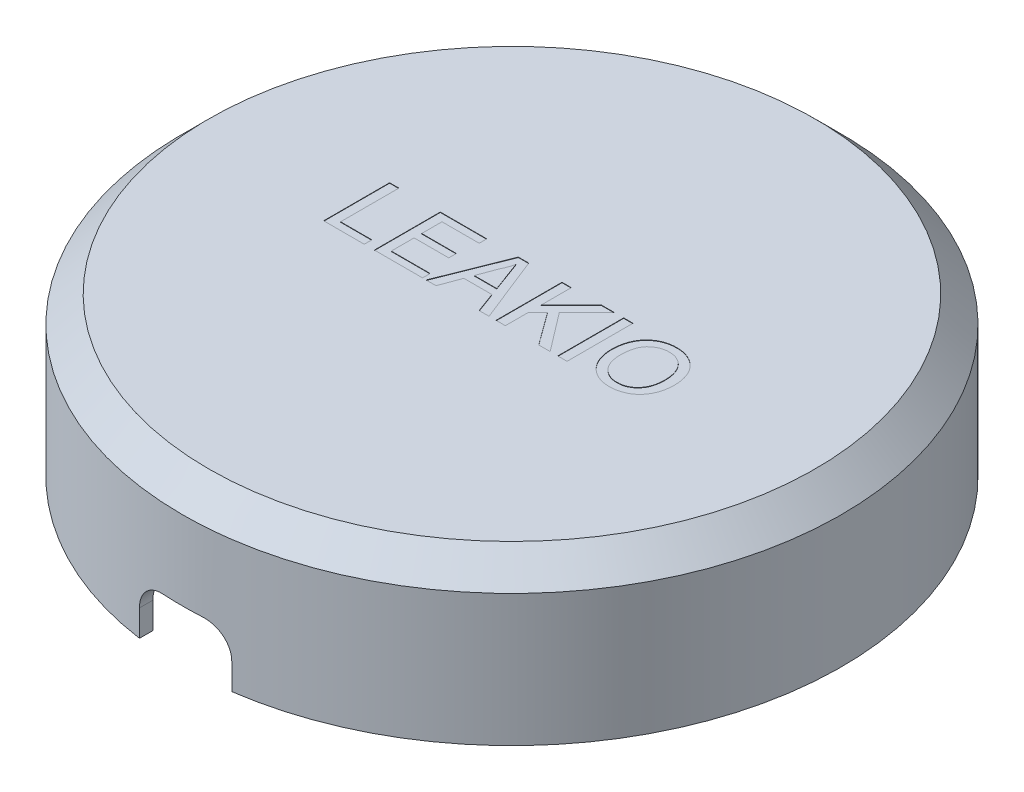
SolidWorks part; units mm, degrees
ref_plane "Front Plane" through (0, 0, 0) normal (0, 0, 1) x (1, 0, 0)
ref_plane "Top Plane" through (0, 0, 0) normal (0, 1, 0) x (1, 0, 0)
ref_plane "Right Plane" through (0, 0, 0) normal (1, 0, 0) x (0, 0, -1)
sketch "Sketch1" plane through (0, 0, 0) normal (0, 1, 0) x (1, 0, 0)
  circle A0 centre (0, 0) radius 25
  dimension "D1" = 50
extrude "Boss-Extrude1" add sketch "Sketch1" along normal blind 12
chamfer "Chamfer1" distance 2 angle 45 1 edges at (0, 12, 25)
shell "Shell2" thickness 1 removed face at (0, 0, 25)
sketch "Sketch4" plane through (0, 12, 0) normal (0, 1, 0) x (1, 0, 0)
  text T0 "LEAKIO" font "Century Gothic" height 5
extrude "Cut-Extrude1" cut sketch "Sketch4" against normal blind 0.05
sketch "Sketch5" plane through (0, 11.95, 0) normal (0, 1, 0) x (1, 0, 0)
  line L0 (5.8129, -2.3369) -> (6.518, -2.3369) construction
  line L1 (6.518, -2.3369) -> (6.518, 2.6631) construction
  line L2 (6.518, 2.6631) -> (5.8129, 2.6631) construction
  line L3 (5.8129, 2.6631) -> (5.8129, -2.3369) construction
  line L4 (1.1334, -2.3369) -> (1.8385, -2.3369) construction
  line L5 (1.8385, -2.3369) -> (1.8385, -0.6062) construction
  line L6 (1.8385, -0.6062) -> (2.5717, 0.126) construction
  line L7 (2.5717, 0.126) -> (4.3676, -2.3369) construction
  line L8 (4.3676, -2.3369) -> (5.2359, -2.3369) construction
  line L9 (5.2359, -2.3369) -> (3.0184, 0.5737) construction
  line L10 (3.0184, 0.5737) -> (5.1077, 2.6631) construction
  line L11 (5.1077, 2.6631) -> (4.1422, 2.6631) construction
  line L12 (4.1422, 2.6631) -> (1.8385, 0.3594) construction
  line L13 (1.8385, 0.3594) -> (1.8385, 2.6631) construction
  line L14 (1.8385, 2.6631) -> (1.1334, 2.6631) construction
  line L15 (1.1334, 2.6631) -> (1.1334, -2.3369) construction
  line L16 (-4.1661, -2.3369) -> (-3.4179, -2.3369) construction
  line L17 (-3.4179, -2.3369) -> (-2.849, -0.7985) construction
  line L18 (-2.849, -0.7985) -> (-0.7176, -0.7985) construction
  line L19 (-0.7176, -0.7985) -> (-0.1487, -2.3369) construction
  line L20 (-0.1487, -2.3369) -> (0.5995, -2.3369) construction
  line L21 (0.5995, -2.3369) -> (-1.3857, 2.6631) construction
  line L22 (-1.3857, 2.6631) -> (-2.1809, 2.6631) construction
  line L23 (-2.1809, 2.6631) -> (-4.1661, -2.3369) construction
  line L24 (-11.9435, -2.3369) -> (-8.8666, -2.3369) construction
  line L25 (-8.8666, -2.3369) -> (-8.8666, -1.76) construction
  line L26 (-8.8666, -1.76) -> (-11.2384, -1.76) construction
  line L27 (-11.2384, -1.76) -> (-11.2384, 2.6631) construction
  line L28 (-11.2384, 2.6631) -> (-11.9435, 2.6631) construction
  line L29 (-11.9435, 2.6631) -> (-11.9435, -2.3369) construction
  line L30 (-8.0974, -2.3369) -> (-4.4435, -2.3369) construction
  line L31 (-4.4435, -2.3369) -> (-4.4435, -1.76) construction
  line L32 (-4.4435, -1.76) -> (-7.3923, -1.76) construction
  line L33 (-7.3923, -1.76) -> (-7.3923, -0.0292) construction
  line L34 (-7.3923, -0.0292) -> (-4.7641, -0.0292) construction
  line L35 (-4.7641, -0.0292) -> (-4.7641, 0.5477) construction
  line L36 (-4.7641, 0.5477) -> (-7.3923, 0.5477) construction
  line L37 (-7.3923, 0.5477) -> (-7.3923, 2.0861) construction
  line L38 (-7.3923, 2.0861) -> (-4.5717, 2.0861) construction
  line L39 (-4.5717, 2.0861) -> (-4.5717, 2.6631) construction
  line L40 (-4.5717, 2.6631) -> (-8.0974, 2.6631) construction
  line L41 (-8.0974, 2.6631) -> (-8.0974, -2.3369) construction
  line L42 (5.8129, -2.3369) -> (6.518, -2.3369)
  line L43 (6.518, -2.3369) -> (6.518, 2.6631)
  line L44 (6.518, 2.6631) -> (5.8129, 2.6631)
  line L45 (5.8129, 2.6631) -> (5.8129, -2.3369)
  line L46 (1.1334, -2.3369) -> (1.8385, -2.3369)
  line L47 (1.8385, -2.3369) -> (1.8385, -0.6062)
  line L48 (1.8385, -0.6062) -> (2.5717, 0.126)
  line L49 (2.5717, 0.126) -> (4.3676, -2.3369)
  line L50 (4.3676, -2.3369) -> (5.2359, -2.3369)
  line L51 (5.2359, -2.3369) -> (3.0184, 0.5737)
  line L52 (3.0184, 0.5737) -> (5.1077, 2.6631)
  line L53 (5.1077, 2.6631) -> (4.1422, 2.6631)
  line L54 (4.1422, 2.6631) -> (1.8385, 0.3594)
  line L55 (1.8385, 0.3594) -> (1.8385, 2.6631)
  line L56 (1.8385, 2.6631) -> (1.1334, 2.6631)
  line L57 (1.1334, 2.6631) -> (1.1334, -2.3369)
  line L58 (-4.1661, -2.3369) -> (-3.4179, -2.3369)
  line L59 (-3.4179, -2.3369) -> (-2.849, -0.7985)
  line L60 (-2.849, -0.7985) -> (-0.7176, -0.7985)
  line L61 (-0.7176, -0.7985) -> (-0.1487, -2.3369)
  line L62 (-0.1487, -2.3369) -> (0.5995, -2.3369)
  line L63 (0.5995, -2.3369) -> (-1.3857, 2.6631)
  line L64 (-1.3857, 2.6631) -> (-2.1809, 2.6631)
  line L65 (-2.1809, 2.6631) -> (-4.1661, -2.3369)
  line L66 (-11.9435, -2.3369) -> (-8.8666, -2.3369)
  line L67 (-8.8666, -2.3369) -> (-8.8666, -1.76)
  line L68 (-8.8666, -1.76) -> (-11.2384, -1.76)
  line L69 (-11.2384, -1.76) -> (-11.2384, 2.6631)
  line L70 (-11.2384, 2.6631) -> (-11.9435, 2.6631)
  line L71 (-11.9435, 2.6631) -> (-11.9435, -2.3369)
  line L72 (-8.0974, -2.3369) -> (-4.4435, -2.3369)
  line L73 (-4.4435, -2.3369) -> (-4.4435, -1.76)
  line L74 (-4.4435, -1.76) -> (-7.3923, -1.76)
  line L75 (-7.3923, -1.76) -> (-7.3923, -0.0292)
  line L76 (-7.3923, -0.0292) -> (-4.7641, -0.0292)
  line L77 (-4.7641, -0.0292) -> (-4.7641, 0.5477)
  line L78 (-4.7641, 0.5477) -> (-7.3923, 0.5477)
  line L79 (-7.3923, 0.5477) -> (-7.3923, 2.0861)
  line L80 (-7.3923, 2.0861) -> (-4.5717, 2.0861)
  line L81 (-4.5717, 2.0861) -> (-4.5717, 2.6631)
  line L82 (-4.5717, 2.6631) -> (-8.0974, 2.6631)
  line L83 (-8.0974, 2.6631) -> (-8.0974, -2.3369)
  line L87 (-2.1248, 1.1627) -> (-2.6367, -0.2216)
  line L88 (-2.6367, -0.2216) -> (-0.9299, -0.2216)
  line L89 (-0.9299, -0.2216) -> (-1.4157, 1.0925)
  line L90 (-2.1248, 1.1627) -> (-2.6367, -0.2216)
  line L91 (-2.6367, -0.2216) -> (-0.9299, -0.2216)
  line L92 (-0.9299, -0.2216) -> (-1.4157, 1.0925)
  spline S0 degree 3 poles (-1990.8776, -80.9604) (28.3072, 11.3576) (6.9256, 5.0645) (7.4324, -0.2247) (7.4537, -0.3826) (7.4853, -0.5387) (7.5249, -0.6927) (7.5747, -0.8442) (7.6313, -0.9941) (7.6985, -1.1403) (7.7729, -1.2828) (7.8571, -1.4174) (7.9486, -1.5453) (8.0503, -1.6636) (8.1583, -1.7769) (8.276, -1.8808) (8.4014, -1.9773) (8.5346, -2.0653) (8.6743, -2.1444) (8.8199, -2.2123) (8.9697, -2.2707) (9.1243, -2.319) (9.2836, -2.3561) (9.4477, -2.3817) (14.9568, -2.9322) (21.5225, 18.8476) (-73.5921, -2000.5828) knots -4.005489 -4.005489 -4.005489 -4.005489 0.042093 0.083554 0.124992 0.166052 0.207381 0.248618 0.290057 0.332021 0.373735 0.415036 0.455409 0.495952 0.536368 0.57703 0.617971 0.659396 0.701152 0.742753 0.784285 0.826186 0.868591 0.911466 0.955303 5.171731 5.171731 5.171731 5.171731 only from (7.4154, 0.097) to (9.7872, -2.401) construction
  spline S1 degree 3 poles (79.5401, -2001.0874) (-1.9272, 16.9385) (4.5006, -2.8844) (10.1044, -2.3838) (10.2591, -2.3594) (10.4115, -2.3267) (10.5611, -2.2835) (10.7075, -2.2302) (10.8511, -2.1676) (10.9922, -2.0972) (11.1278, -2.0167) (11.2557, -1.9257) (11.3761, -1.8266) (11.4887, -1.7184) (11.592, -1.6002) (11.6885, -1.474) (11.7766, -1.3383) (11.8566, -1.1944) (11.9272, -1.0432) (11.9898, -0.8869) (12.0415, -0.7251) (12.085, -0.5587) (12.1175, -0.3872) (12.142, -0.2111) (12.6417, 6.2939) (-7.2229, 13.4753) (2011.3267, -53.0079) knots -4.181962 -4.181962 -4.181962 -4.181962 0.040917 0.081206 0.121044 0.160801 0.20044 0.240141 0.27998 0.320332 0.360792 0.400579 0.440342 0.480112 0.519955 0.560443 0.601634 0.64374 0.686389 0.729297 0.772543 0.816374 0.860888 0.906038 0.95244 5.851848 5.851848 5.851848 5.851848 only from (9.7872, -2.401) to (12.159, 0.155) construction
  spline S2 degree 3 poles (2011.6534, 42.3167) (-6.1458, -13.5317) (12.6181, -6.2393) (12.1431, 0.5155) (12.1192, 0.6892) (12.0892, 0.8584) (12.0474, 1.0224) (11.9975, 1.1812) (11.9394, 1.3357) (11.8714, 1.4841) (11.7953, 1.6269) (11.7106, 1.762) (11.6167, 1.8882) (11.5166, 2.0079) (11.406, 2.1173) (11.2886, 2.2201) (11.1628, 2.3147) (11.029, 2.4003) (10.8892, 2.4768) (10.7453, 2.5452) (10.5961, 2.6004) (10.4431, 2.6471) (10.286, 2.6827) (10.1245, 2.7093) (4.3785, 3.2257) (-2.1734, -17.2366) (74.9237, 2001.6053) knots -5.029529 -5.029529 -5.029529 -5.029529 0.046666 0.092161 0.136649 0.180448 0.223293 0.265781 0.307491 0.349241 0.390297 0.430963 0.470884 0.510312 0.549967 0.589534 0.629402 0.66999 0.710719 0.750975 0.79155 0.832033 0.873092 0.914413 0.956901 5.273034 5.273034 5.273034 5.273034 only from (12.159, 0.155) to (9.7902, 2.7272) construction
  spline S3 degree 3 poles (-111.2079, 1998.9844) (24.1505, -24.2354) (15.7546, 3.5944) (9.2921, 2.6869) (9.0587, 2.6336) (8.8372, 2.5574) (8.6283, 2.4581) (8.431, 2.3379) (8.2471, 2.1938) (8.0745, 2.0316) (7.9199, 1.848) (7.7833, 1.648) (7.6701, 1.4296) (7.577, 1.1953) (7.5036, 0.9445) (7.4522, 0.6769) (6.5923, -7.0534) (33.92, -16.1975) (-1990.7427, 84.2629) knots -4.703221 -4.703221 -4.703221 -4.703221 0.064217 0.125675 0.185372 0.243705 0.301102 0.358698 0.416748 0.476136 0.536238 0.596504 0.657597 0.72047 0.7855 0.853425 0.924774 6.615557 6.615557 6.615557 6.615557 only from (9.7902, 2.7272) to (7.4154, 0.097) construction
  spline S4 degree 3 poles (7.4154, 0.097) (7.416, 0.0428) (7.4171, -0.0646) (7.4324, -0.2247) (7.4537, -0.3826) (7.4853, -0.5387) (7.5249, -0.6927) (7.5747, -0.8442) (7.6313, -0.9941) (7.6985, -1.1403) (7.7729, -1.2828) (7.8571, -1.4174) (7.9486, -1.5453) (8.0503, -1.6636) (8.1583, -1.7769) (8.276, -1.8808) (8.4014, -1.9773) (8.5346, -2.0653) (8.6743, -2.1444) (8.8199, -2.2123) (8.9697, -2.2707) (9.1243, -2.319) (9.2836, -2.3561) (9.4477, -2.3817) (9.6159, -2.3985) (9.7298, -2.4002) (9.7872, -2.401) knots 0 0 0 0 0.042093 0.083554 0.124992 0.166052 0.207381 0.248618 0.290057 0.332021 0.373735 0.415036 0.455409 0.495952 0.536368 0.57703 0.617971 0.659396 0.701152 0.742753 0.784285 0.826186 0.868591 0.911466 0.955303 1 1 1 1
  spline S5 degree 3 poles (9.7872, -2.401) (9.8407, -2.4) (9.9467, -2.3979) (10.1044, -2.3838) (10.2591, -2.3594) (10.4115, -2.3267) (10.5611, -2.2835) (10.7075, -2.2302) (10.8511, -2.1676) (10.9922, -2.0972) (11.1278, -2.0167) (11.2557, -1.9257) (11.3761, -1.8266) (11.4887, -1.7184) (11.592, -1.6002) (11.6885, -1.474) (11.7766, -1.3383) (11.8566, -1.1944) (11.9272, -1.0432) (11.9898, -0.8869) (12.0415, -0.7251) (12.085, -0.5587) (12.1175, -0.3872) (12.142, -0.2111) (12.1559, -0.0298) (12.158, 0.0929) (12.159, 0.155) knots 0 0 0 0 0.040917 0.081206 0.121044 0.160801 0.20044 0.240141 0.27998 0.320332 0.360792 0.400579 0.440342 0.480112 0.519955 0.560443 0.601634 0.64374 0.686389 0.729297 0.772543 0.816374 0.860888 0.906038 0.95244 1 1 1 1
  spline S6 degree 3 poles (12.159, 0.155) (12.1579, 0.2162) (12.1556, 0.3369) (12.1431, 0.5155) (12.1192, 0.6892) (12.0892, 0.8584) (12.0474, 1.0224) (11.9975, 1.1812) (11.9394, 1.3357) (11.8714, 1.4841) (11.7953, 1.6269) (11.7106, 1.762) (11.6167, 1.8882) (11.5166, 2.0079) (11.406, 2.1173) (11.2886, 2.2201) (11.1628, 2.3147) (11.029, 2.4003) (10.8892, 2.4768) (10.7453, 2.5452) (10.5961, 2.6004) (10.4431, 2.6471) (10.286, 2.6827) (10.1245, 2.7093) (9.9588, 2.7242) (9.8467, 2.7262) (9.7902, 2.7272) knots 0 0 0 0 0.046666 0.092161 0.136649 0.180448 0.223293 0.265781 0.307491 0.349241 0.390297 0.430963 0.470884 0.510312 0.549967 0.589534 0.629402 0.66999 0.710719 0.750975 0.79155 0.832033 0.873092 0.914413 0.956901 1 1 1 1
  spline S7 degree 3 poles (9.7902, 2.7272) (9.7046, 2.7252) (9.5371, 2.7213) (9.2921, 2.6869) (9.0587, 2.6336) (8.8372, 2.5574) (8.6283, 2.4581) (8.431, 2.3379) (8.2471, 2.1938) (8.0745, 2.0316) (7.9199, 1.848) (7.7833, 1.648) (7.6701, 1.4296) (7.577, 1.1953) (7.5036, 0.9445) (7.4522, 0.6769) (7.4206, 0.3925) (7.4172, 0.1972) (7.4154, 0.097) knots 0 0 0 0 0.064217 0.125675 0.185372 0.243705 0.301102 0.358698 0.416748 0.476136 0.536238 0.596504 0.657597 0.72047 0.7855 0.853425 0.924774 1 1 1 1
  spline S10 degree 3 poles (2887.5316, -804.8663) (-29.6975, 25.5683) (0.6009, 8.9195) (-1.921, 1.616) (-4.9185, -5.9032) (-38.2173, 0.4292) (2719.4714, -1260.7247) knots -22.708305 -22.708305 -22.708305 -22.708305 0.247294 0.495608 0.746359 24.824677 24.824677 24.824677 24.824677 only from (-1.7833, 2.0861) to (-2.1248, 1.1627)
  spline S11 degree 3 poles (2824.5708, 1007.4934) (-4.781, -27.0341) (2.9793, -10.5779) (-1.525, 1.3868) (-1.5746, 1.5238) (-1.6233, 1.6516) (-1.6672, 1.7719) (-1.7077, 1.8841) (-4.1671, 8.2264) (8.0295, 19.9743) (-2820.4599, -1024.2915) knots -35.765737 -35.765737 -35.765737 -35.765737 0.153148 0.299433 0.436426 0.565671 0.686508 0.799269 0.903395 19.947809 19.947809 19.947809 19.947809 only from (-1.4157, 1.0925) to (-1.7833, 2.0861)
  spline S12 degree 3 poles (-1.7833, 2.0861) (-1.8024, 2.007) (-1.8407, 1.8484) (-1.921, 1.616) (-2.0128, 1.3857) (-2.0873, 1.2373) (-2.1248, 1.1627) knots 0 0 0 0 0.247294 0.495608 0.746359 1 1 1 1
  spline S13 degree 3 poles (-1.4157, 1.0925) (-1.4343, 1.1433) (-1.4707, 1.2426) (-1.525, 1.3868) (-1.5746, 1.5238) (-1.6233, 1.6516) (-1.6672, 1.7719) (-1.7077, 1.8841) (-1.7477, 1.9873) (-1.7717, 2.054) (-1.7833, 2.0861) knots 0 0 0 0 0.153148 0.299433 0.436426 0.565671 0.686508 0.799269 0.903395 1 1 1 1
  dimension "D1" = 0
extrude "Boss-Extrude2" add sketch "Sketch5" along normal blind 0.02
sketch "Sketch6" plane through (0, 0, 0) normal (0, 0, 1) x (1, 0, 0)
  line L0 (-25, 0) -> (25, 0) construction
  line L1 (-3.5, 0) -> (3.5, 0)
  line L2 (-3.5, 0) -> (-3.5, 4)
  line L3 (-3.5, 4) -> (3.5, 4)
  line L4 (3.5, 0) -> (3.5, 4)
  line L5 (0, 4) -> (0, 0) construction
  dimension "D1" = 7
  dimension "D2" = 4
extrude "Cut-Extrude2" cut sketch "Sketch6" along normal through all
fillet "Fillet1" radius 2 2 edges at (3.5, 4, 24.2486) (-3.5, 4, 24.2486)
sketch "Sketch7" plane through (0, 11, 0) normal (0, -1, 0) x (1, 0, 0)
  line L1 (-15, 15) -> (15, 15) construction
  line L2 (-15, 15) -> (-15, -15) construction
  line L3 (-15, -15) -> (15, -15) construction
  line L4 (15, 15) -> (15, -15) construction
  line L5 (-15, 15) -> (15, -15) construction
  line L6 (-15, -15) -> (15, 15) construction
  circle A0 centre (-15, 15) radius 1.5
  circle A1 centre (15, 15) radius 1.5
  circle A2 centre (-15, -15) radius 1.5
  circle A3 centre (15, -15) radius 1.5
  point P0 (0, 0)
  dimension "D2" = 3
  dimension "D3" = 3
  dimension "D4" = 3
  dimension "D5" = 3
  dimension "D1" = 30
extrude "Boss-Extrude3" add sketch "Sketch7" along normal up to surface (11 mm away) up to face at (0, 0, -0.1257)
sketch "Sketch8" plane through (0, 11, 0) normal (0, -1, 0) x (1, 0, 0)
  line L0 (-16, 0) -> (16, 0) construction
  line L1 (-16, 10) -> (-14, 10)
  line L2 (-16, 10) -> (-16, -10)
  line L3 (-16, -10) -> (-14, -10)
  line L4 (-14, 10) -> (-14, -10)
  line L5 (14, 10) -> (16, 10)
  line L6 (14, 10) -> (14, -10)
  line L7 (14, -10) -> (16, -10)
  line L8 (16, 10) -> (16, -10)
  dimension "D1" = 2
  dimension "D2" = 32
  dimension "D3" = 20
extrude "Boss-Extrude4" add sketch "Sketch8" along normal blind 2
sketch "Sketch9" plane through (0, 0, 0) normal (0, -1, 0) x (1, 0, 0)
  circle A0 centre (-15, 15) radius 1
  circle A1 centre (15, 15) radius 1
  circle A2 centre (15, -15) radius 1
  circle A3 centre (-15, -15) radius 1
  dimension "D1" = 2
  dimension "D2" = 2
  dimension "D3" = 2
  dimension "D4" = 2
extrude "Cut-Extrude3" cut sketch "Sketch9" against normal blind 4
